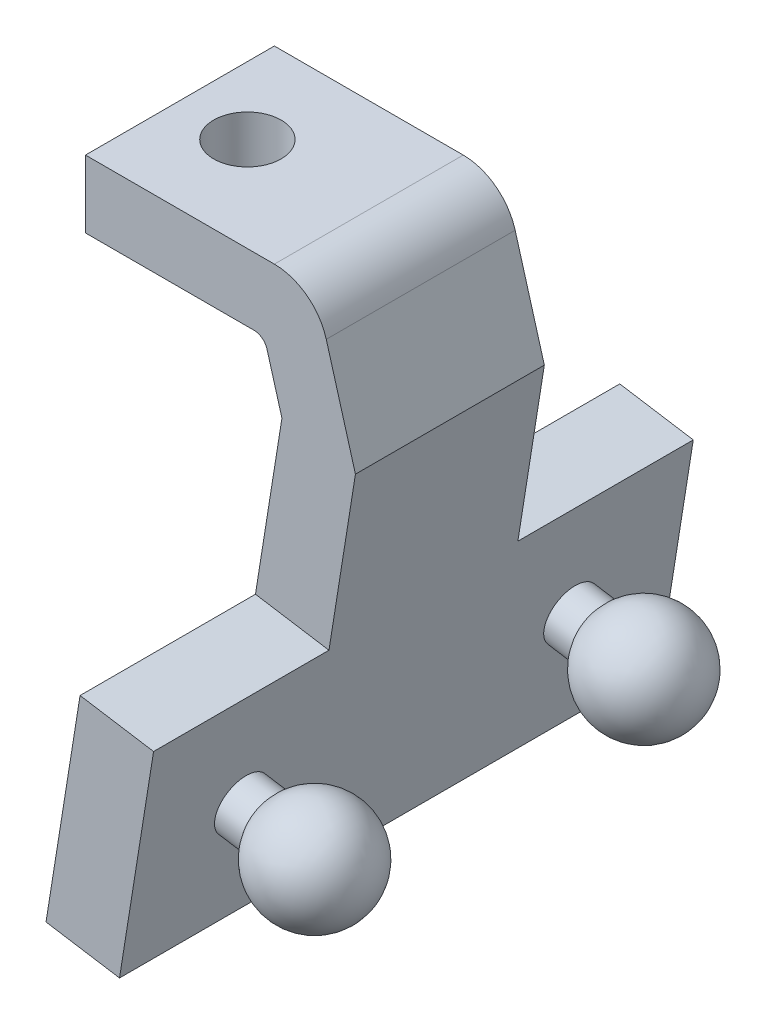
SolidWorks part; units mm, degrees
ref_plane "前视基准面" through (0, 0, 0) normal (0, 0, 1) x (1, 0, 0)
ref_plane "上视基准面" through (0, 0, 0) normal (0, 1, 0) x (1, 0, 0)
ref_plane "右视基准面" through (0, 0, 0) normal (1, 0, 0) x (0, 0, -1)
other "Configuration Table"
sketch "草图1" plane through (0, 0, 0) normal (0, 0, 1) x (1, 0, 0)
  line L0 (0, 0) -> (6.2454, 0)
  line L1 (6.7262, -0.3628) -> (7.2802, -2.304)
  line L2 (7.2802, -2.304) -> (5.0378, -16.3443)
  line L3 (5.0378, -16.3443) -> (7.7617, -16.7793)
  line L4 (7.7617, -16.7793) -> (10.0041, -2.7391)
  line L5 (10.0041, -2.7391) -> (8.9232, 1.0488)
  line L6 (0, 2.5) -> (7, 2.5)
  line L7 (0, 0) -> (0, 2.5)
  arc A0 (6.2454, 0) -> (6.7262, -0.3628) centre (6.2454, -0.5) cw
  arc A1 (8.9232, 1.0488) -> (7, 2.5) centre (7, 0.5) ccw
  dimension "D1" = 7
  dimension "D3" = 2
  dimension "D6" = 0.5
  dimension "D2" = 2.5
  dimension "D4" = 155
  dimension "D5" = 2.5
extrude "凸台-拉伸1" add sketch "草图1" along normal mid plane 7
sketch "草图2" plane through (0, 0, 0) normal (0, -1, 0) x (1, 0, 0)
  circle A0 centre (2.5, 0) radius 1.25
  dimension "D1" = 2.5
  dimension "D2" = 2.5
extrude "切除-拉伸3" cut sketch "草图2" against normal blind 5.5
sketch "草图3" plane through (10.1818, -1.6261, 0) normal (0.9875, -0.1577, 0) x (0, 0, -1)
  line L0 (-3.5, -15.3452) -> (3.5, -15.3452) construction
  line L1 (-10, -7.3452) -> (10, -7.3452)
  line L2 (-10, -7.3452) -> (-10, -15.3452)
  line L3 (-10, -15.3452) -> (10, -15.3452)
  line L4 (10, -7.3452) -> (10, -15.3452)
  line L5 (-10, -7.3452) -> (10, -15.3452) construction
  line L6 (-10, -15.3452) -> (10, -7.3452) construction
  point P0 (0, -11.3452)
  dimension "D1" = 20
  dimension "D2" = 8
extrude "凸台-拉伸2" add sketch "草图3" against normal up to vertex (2.7584 mm away) up to point (5.0378, -16.3443, -3.5)
sketch "草图4" plane through (10.1818, -1.6261, 0) normal (0.9875, -0.1577, 0) x (0, 0, -1)
  line L0 (-10, -15.3452) -> (10, -15.3452) construction
  circle A0 centre (-6.0994, -11.3452) radius 1
  point P2 (-6.0994, -11.2672)
  dimension "D1" = 2
  dimension "D2" = 4
extrude "凸台-拉伸3" add sketch "草图4" along normal blind 1
ref_axis "基准轴1" through (9.3555, -12.9832, 6.0994) along (-0.9875, 0.1577, 0)
ref_plane "基准面1" through (-1.7893, -11.2033, 0) normal (0.1577, 0.9875, 0) x (-0.9875, 0.1577, 0)
sketch "草图5" plane through (-1.7893, -11.2033, 0) normal (0.1577, 0.9875, 0) x (-0.9875, 0.1577, 0)
  line L0 (-11.3109, 6.0994) -> (-15.0429, 6.0994)
  line L1 (-11.3109, 7.0994) -> (-11.3109, 5.0994) construction
  line L2 (-11.3109, 6.0994) -> (-11.3109, 7.0994)
  arc A0 (-11.3109, 7.0994) -> (-15.0429, 6.0994) centre (-13.0429, 6.0994) ccw
  dimension "D1" = 4
revolve "旋转1" add sketch "草图5" angle 360 about L0
mirror "镜向1" about plane through (0, 0, 0) normal (0, 0, 1) of "凸台-拉伸3", "旋转1"
